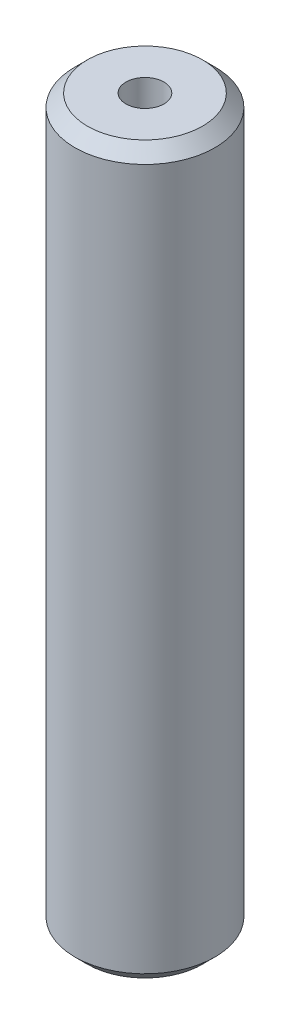
SolidWorks part; units mm, degrees
ref_plane "Front Plane" through (0, 0, 0) normal (0, 0, 1) x (1, 0, 0)
ref_plane "Top Plane" through (0, 0, 0) normal (0, 1, 0) x (1, 0, 0)
ref_plane "Right Plane" through (0, 0, 0) normal (1, 0, 0) x (0, 0, -1)
sketch "Sketch1" plane through (0, 0, 0) normal (0, 1, 0) x (1, 0, 0)
  circle A0 centre (0, 0) radius 10
  dimension "SHAFT_OD" = 20
extrude "Boss-Extrude1" add sketch "Sketch1" along normal blind 103.7056
sketch "Sketch2" plane through (0, 0, 0) normal (0, 1, 0) x (1, 0, 0)
  circle A0 centre (0, 0) radius 2.7156
  dimension "BORE_D" = 5.4312
extrude "Cut-Extrude1" cut sketch "Sketch2" along normal through all
chamfer "Chamfer1" distance 1.7773 angle 45 2 edges at (0, 103.7056, 10) (0, 0, 10)
